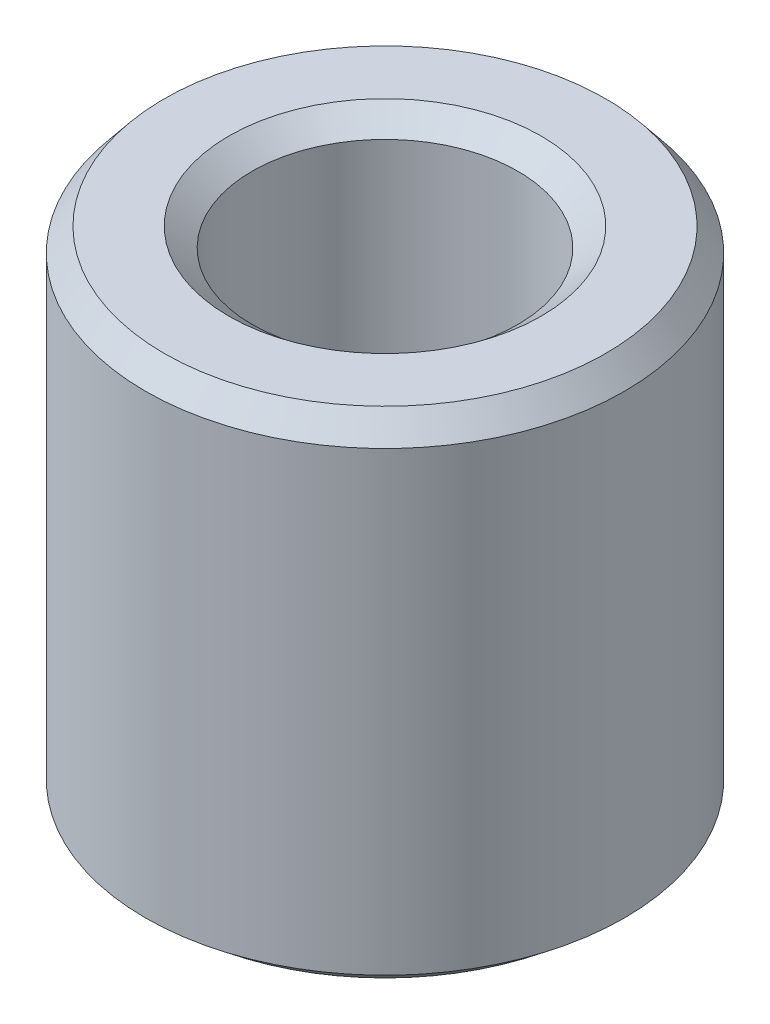
SolidWorks part; units mm, degrees
ref_plane "Front Plane" through (0, 0, 0) normal (0, 0, 1) x (1, 0, 0)
ref_plane "Top Plane" through (0, 0, 0) normal (0, 1, 0) x (1, 0, 0)
ref_plane "Right Plane" through (0, 0, 0) normal (1, 0, 0) x (0, 0, -1)
sketch "Sketch1" plane through (0, 0, 0) normal (0, 1, 0) x (1, 0, 0)
  circle A0 centre (0, 0) radius 30
  dimension "SLEEVE_OD" = 60
extrude "Boss-Extrude1" add sketch "Sketch1" along normal blind 62.411
sketch "Sketch2" plane through (0, 0, 0) normal (0, 1, 0) x (1, 0, 0)
  circle A0 centre (0, 0) radius 16.6403
  dimension "BORE_D" = 33.2806
extrude "Cut-Extrude1" cut sketch "Sketch2" along normal through all
chamfer "Chamfer1" distance 2.9167 angle 38.972 4 edges at (0, 62.411, 16.6403) (0, 0, 16.6403) (0, 0, 30) (0, 62.411, 30) first distance on face at (0, 62.411, 16.6403) first distance on face at (0, 0, 16.6403) first distance on face at (0, 62.411, 30)
